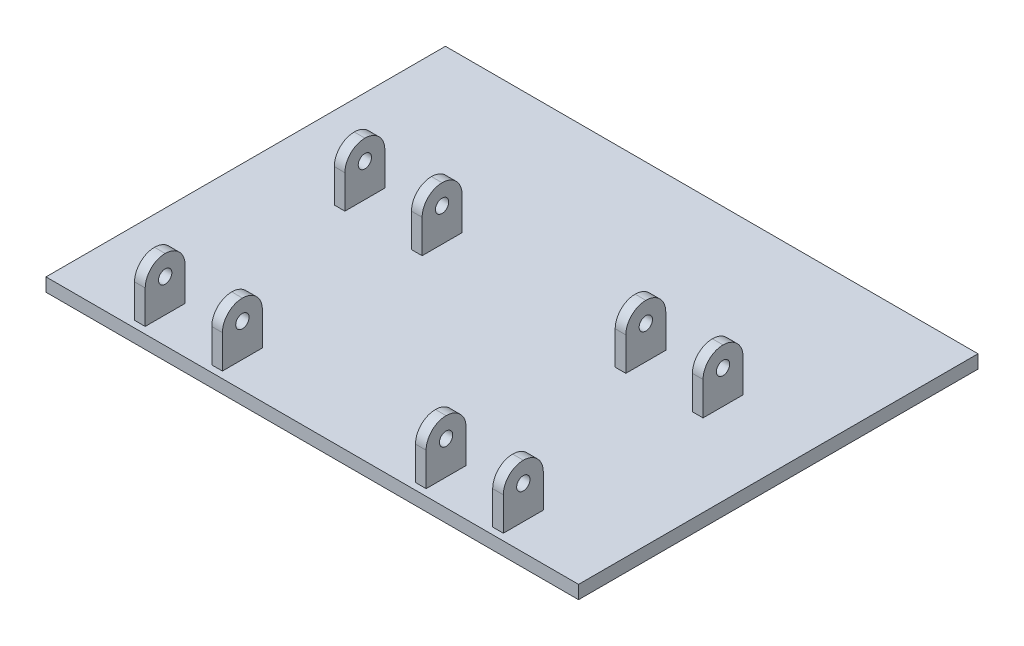
SolidWorks part; units mm, degrees
ref_plane "Front Plane" through (0, 0, 0) normal (0, 0, 1) x (1, 0, 0)
ref_plane "Top Plane" through (0, 0, 0) normal (0, 1, 0) x (1, 0, 0)
ref_plane "Right Plane" through (0, 0, 0) normal (1, 0, 0) x (0, 0, -1)
sketch "Sketch1" plane through (0, 0, 0) normal (0, 1, 0) x (1, 0, 0)
  line L1 (200, -150) -> (-200, -150)
  line L2 (200, -150) -> (200, 150)
  line L3 (200, 150) -> (-200, 150)
  line L4 (-200, -150) -> (-200, 150)
  line L5 (200, -150) -> (-200, 150) construction
  line L6 (200, 150) -> (-200, -150) construction
  point P0 (0, 0)
  dimension "D1" = 300
  dimension "D2" = 400
extrude "Boss-Extrude1" add sketch "Sketch1" along normal blind 10
sketch "Sketch2" plane through (0, 10, 0) normal (0, 1, 0) x (1, 0, 0)
  line L0 (-105.5, -115) -> (-105.5, -145) construction
  line L21 (-138.5, -115) -> (-72.5, -115)
  line L22 (-138.5, -115) -> (-138.5, -145)
  line L23 (-138.5, -145) -> (-72.5, -145)
  line L24 (-72.5, -115) -> (-72.5, -145)
  line L25 (-138.5, -145) -> (-130.5, -145)
  line L26 (-72.5, -115) -> (-80.5, -115)
  line L27 (-72.5, -115) -> (-72.5, -145)
  line L28 (-72.5, -145) -> (-80.5, -145)
  line L29 (-80.5, -115) -> (-80.5, -145)
  line L30 (-130.5, -115) -> (-130.5, -145)
  line L31 (-138.5, -115) -> (-130.5, -115)
  line L32 (-138.5, -115) -> (-138.5, -145)
  line L33 (0, 150) -> (0, -150) construction
  line L34 (200, 150) -> (-200, 150) construction
  line L35 (-200, -150) -> (200, -150) construction
  line L36 (105.5, -115) -> (105.5, -145) construction
  line L37 (138.5, -115) -> (138.5, -145)
  line L38 (138.5, -115) -> (130.5, -115)
  line L39 (130.5, -115) -> (130.5, -145)
  line L40 (80.5, -115) -> (80.5, -145)
  line L41 (72.5, -145) -> (80.5, -145)
  line L42 (72.5, -115) -> (72.5, -145)
  line L43 (72.5, -115) -> (80.5, -115)
  line L44 (138.5, -145) -> (130.5, -145)
  line L45 (72.5, -115) -> (72.5, -145)
  line L46 (138.5, -145) -> (72.5, -145)
  line L47 (138.5, -115) -> (138.5, -145)
  line L48 (138.5, -115) -> (72.5, -115)
  dimension "D1" = 30
  dimension "D2" = 50
  dimension "D3" = 8
  dimension "D4" = 261
  dimension "D5" = 5
extrude "Boss-Extrude2" add sketch "Sketch2" along normal blind 40 contours L30 L21 L22 L23 | L21 L29 L23 L24 | L43 L42 L41 L40 | L44 L37 L38 L39 region at (-134.5, 10, 130) region at (-76.5, 10, 130) region at (134.5, 10, 130) region at (76.5, 10, 130)
sketch "Sketch3" plane through (138.5, 0, 0) normal (1, 0, 0) x (0, 0, -1)
  line L0 (-115, 50) -> (-145, 50) construction
  line L1 (-115, 50) -> (-115, 10) construction
  circle A0 centre (-130, 35) radius 5
  circle A1 centre (-130, 35) radius 15
  point P6 (-130, 20.6554)
  dimension "D1" = 10
  dimension "D2" = 30
extrude "Cut-Extrude1" cut sketch "Sketch3" against normal through all contours A0
fillet "Fillet1" radius 15 8 edges at (134.5, 50, 115) (134.5, 50, 145) (76.5, 50, 145) (76.5, 50, 115) (-76.5, 50, 115) (-134.5, 50, 115) (-76.5, 50, 145) (-134.5, 50, 145)
sketch "Sketch4" plane through (0, 10, 0) normal (0, 1, 0) x (1, 0, 0)
  line L0 (-105.5, 35) -> (-105.5, 5) construction
  line L5 (-80.5, 35) -> (-72.5, 35)
  line L6 (-80.5, 35) -> (-80.5, 5)
  line L7 (-80.5, 5) -> (-72.5, 5)
  line L8 (-72.5, 35) -> (-72.5, 5)
  line L9 (-72.5, 35) -> (-138.5, 35)
  line L10 (-72.5, 35) -> (-72.5, 5)
  line L11 (-72.5, 5) -> (-138.5, 5)
  line L12 (-138.5, 35) -> (-138.5, 5)
  line L13 (-130.5, 5) -> (-138.5, 5)
  line L14 (-138.5, 35) -> (-138.5, 5)
  line L15 (-130.5, 35) -> (-138.5, 35)
  line L16 (-130.5, 35) -> (-130.5, 5)
  line L17 (0, 150) -> (0, -150) construction
  line L18 (200, 150) -> (-200, 150) construction
  line L19 (-200, -150) -> (200, -150) construction
  line L20 (105.5, 35) -> (105.5, 5) construction
  line L21 (130.5, 35) -> (130.5, 5)
  line L22 (130.5, 35) -> (138.5, 35)
  line L23 (138.5, 35) -> (138.5, 5)
  line L24 (130.5, 5) -> (138.5, 5)
  line L25 (138.5, 35) -> (138.5, 5)
  line L26 (72.5, 5) -> (138.5, 5)
  line L27 (72.5, 35) -> (72.5, 5)
  line L28 (72.5, 35) -> (138.5, 35)
  line L29 (72.5, 35) -> (72.5, 5)
  line L30 (80.5, 5) -> (72.5, 5)
  line L31 (80.5, 35) -> (80.5, 5)
  line L32 (80.5, 35) -> (72.5, 35)
  line L33 (-138.5, -115) -> (-130.5, -115) construction
  dimension "D4" = 261
  dimension "D1" = 8
  dimension "D2" = 30
  dimension "D3" = 50
  dimension "D5" = 120
extrude "Boss-Extrude3" add sketch "Sketch4" along normal blind 40 contours L16 L9 L12 L11 | L8 L5 L6 L7 | L21 L24 L23 L22 | L31 L28 L27 L26 region at (-76.5, 10, -20) region at (-134.5, 10, -20) region at (134.5, 10, -20) region at (76.5, 10, -20)
sketch "Sketch5" plane through (138.5, 0, 0) normal (1, 0, 0) x (0, 0, -1)
  line L0 (35, 50) -> (5, 50) construction
  line L1 (5, 50) -> (5, 10) construction
  circle A0 centre (20, 35) radius 5
  circle A1 centre (20, 35) radius 15
  point P6 (20, 50)
  dimension "D1" = 10
extrude "Cut-Extrude2" cut sketch "Sketch5" against normal through all contours A0
fillet "Fillet2" radius 15 8 edges at (-134.5, 50, -35) (-76.5, 50, -35) (134.5, 50, -35) (76.5, 50, -35) (-134.5, 50, -5) (-76.5, 50, -5) (76.5, 50, -5) (134.5, 50, -5)
equation "\"LowerArmDist\"=261"
equation "\"D4@Sketch2\"=\"LowerArmDist\""
equation "\"LowerHeight\"=5"
equation "\"D5@Sketch2\"=\"LowerHeight\""
equation "\"UpperArmDist\"=261"
equation "\"D4@Sketch4\"=\"UpperArmDist\""
equation "\"UpperHeight\"=120"
equation "\"D5@Sketch4\"=\"UpperHeight\""
